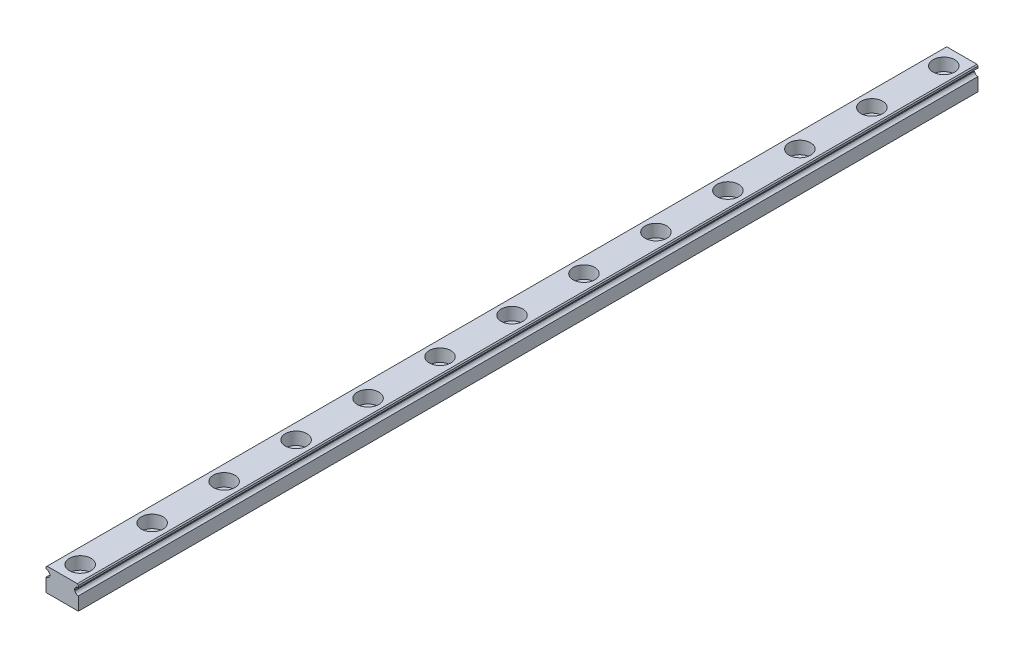
SolidWorks part; units mm, degrees
ref_plane "Спереди" through (0, 0, 0) normal (0, 0, 1) x (1, 0, 0)
ref_plane "Сверху" through (0, 0, 0) normal (0, 1, 0) x (1, 0, 0)
ref_plane "Справа" through (0, 0, 0) normal (1, 0, 0) x (0, 0, -1)
sketch "Sketch1" plane through (0, 0, 0) normal (0, 0, 1) x (1, 0, 0)
  line L0 (0, 0) -> (0, 5.7299) construction
  line L1 (-4.5, -3.25) -> (4.5, -3.25)
  line L2 (-4.5, -3.25) -> (-4.5, 0.45)
  line L3 (-4.5, 3.25) -> (4.5, 3.25)
  line L4 (4.5, -3.25) -> (4.5, 0.45)
  line L5 (-4.5, -3.25) -> (4.5, 3.25) construction
  line L6 (-4.5, 3.25) -> (4.5, -3.25) construction
  line L7 (-4.5, 2.45) -> (-4.5, 3.25)
  line L8 (-3.5318, 1.2) -> (-3.4, 1.2)
  line L9 (3.5318, 1.2) -> (3.4, 1.2)
  line L10 (-3.5318, 1.7) -> (-3.4, 1.7)
  line L11 (-3.4, 1.2) -> (-3.4, 1.7)
  line L12 (3.4, 1.2) -> (3.4, 1.7)
  line L13 (3.5318, 1.7) -> (3.4, 1.7)
  line L14 (4.5, 2.45) -> (4.5, 3.25)
  line L15 (-3.4, 1.45) -> (-4.5, 1.45) construction
  arc A0 (-3.5318, 1.7) -> (-4.5, 2.45) centre (-4.5, 1.45) ccw
  arc A1 (-4.5, 0.45) -> (-3.5318, 1.2) centre (-4.5, 1.45) ccw
  arc A2 (4.5, 0.45) -> (3.5318, 1.2) centre (4.5, 1.45) cw
  arc A3 (3.5318, 1.7) -> (4.5, 2.45) centre (4.5, 1.45) cw
  point P0 (0, 0)
  dimension "D3" = 1
  dimension "D1" = 9
  dimension "D2" = 6.5
  dimension "D4" = 2.05
  dimension "D5" = 6.8
  dimension "D6" = 0.5
extrude "Extrude1" add sketch "Sketch1" along normal blind 250
sketch "Sketch2" plane through (0, 3.25, 0) normal (0, 1, 0) x (1, 0, 0)
  line L0 (4.5, 0) -> (-4.5, 0) construction
  circle A0 centre (0, -5) radius 1.75
  circle A1 centre (0, -5) radius 3
  dimension "D1" = 3.5
  dimension "D2" = 6
  dimension "D3" = 5
extrude "Extrude2" cut sketch "Sketch2" against normal blind 3.5 contours A1
extrude "Extrude3" cut sketch "Sketch" against normal through all contours A0
sketch "Sketch" plane through (0, 3.25, 0) normal (0, 1, 0) x (1, 0, 0) same geometry as "Sketch2"
pattern_linear "LPattern1" count 40 spacing 20 along (0, 0, 1) of "Extrude2", "Extrude3"
chamfer "Chamfer1" distance 0.3 angle 45 2 edges at (4.5, 3.25, 125) (-4.5, 3.25, 125)
